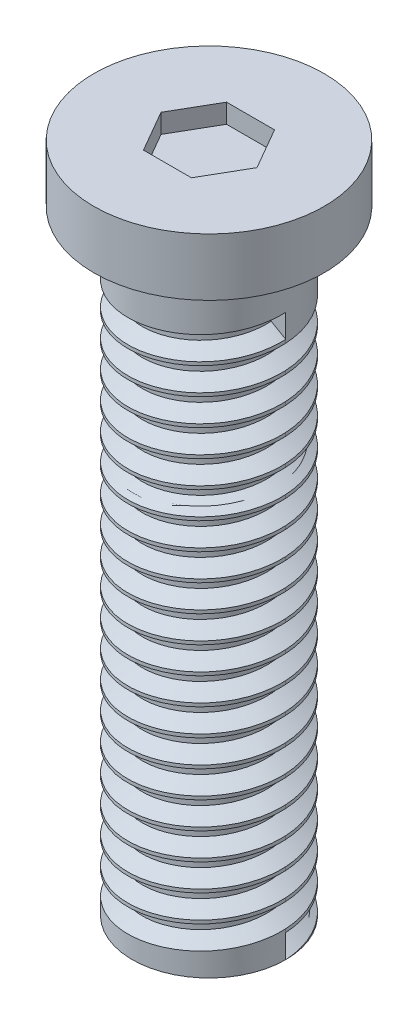
SolidWorks part; units mm, degrees
ref_plane "Front" through (0, 0, 0) normal (0, 0, 1) x (1, 0, 0)
ref_plane "Top" through (0, 0, 0) normal (0, 1, 0) x (1, 0, 0)
ref_plane "Right" through (0, 0, 0) normal (1, 0, 0) x (0, 0, -1)
sketch "Sketch1" plane through (0, 0, 0) normal (0, 1, 0) x (1, 0, 0)
  circle A0 centre (0, 0) radius 2
  dimension "D1" = 4
extrude "Boss-Extrude1" add sketch "Sketch1" along normal blind 16
sketch "Sketch2" plane through (0, 16, 0) normal (0, 1, 0) x (1, 0, 0)
  circle A1 centre (0, 0) radius 3
  dimension "D1" = 6
extrude "Boss-Extrude2" add sketch "Sketch2" along normal blind 1.5
sketch "Sketch3" plane through (0, 17.5, 0) normal (0, 1, 0) x (1, 0, 0)
  line L1 (0.625, -1.0825) -> (1.25, 0)
  line L2 (1.25, 0) -> (0.625, 1.0825)
  line L3 (0.625, 1.0825) -> (-0.625, 1.0825)
  line L4 (-0.625, 1.0825) -> (-1.25, 0)
  line L5 (-1.25, 0) -> (-0.625, -1.0825)
  line L6 (-0.625, -1.0825) -> (0.625, -1.0825)
  circle A0 centre (0, 0) radius 1.0825 construction
  dimension "D1" = 1.25
extrude "Cut-Extrude1" cut sketch "Sketch3" against normal blind 0.5
thread "Thread1" pitch 0.7 method cut profile "Thread Profile1" start angle 0, offset 0, length 14, pitch 0.7, diameter 4
ref_plane "Plane1" through (2, 0, 0) normal (0, 0, 1) x (1, 0, 0)
sketch "Thread Profile1" plane through (2, 0, 0) normal (0, 0, 1) x (1, 0, 0)
  line L0 (0, 0) -> (0, 0.7) construction
  line L11 (0, 0) -> (0, 0.6125)
  line L12 (0, 0.6125) -> (-0.3789, 0.3937)
  line L13 (-0.3789, 0.3937) -> (-0.3789, 0.2187)
  line L15 (-0.3789, 0.2187) -> (0, 0)
  line L17 (-0.3789, 0.3062) -> (0, 0.3062) construction
  point P2 (0, 0)
  dimension "Pitch" = 0.7
  dimension "Profile_Angle" = 60
  dimension "Profile_Land" = 0.175
  dimension "Profile_Height" = 0.3789
